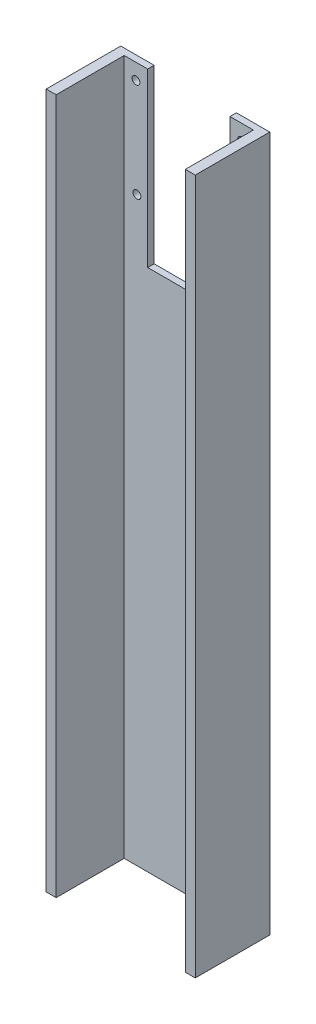
SolidWorks part; units mm, degrees
ref_plane "Front" through (0, 0, 0) normal (0, 0, 1) x (1, 0, 0)
ref_plane "Top" through (0, 0, 0) normal (0, 1, 0) x (1, 0, 0)
ref_plane "Right" through (0, 0, 0) normal (1, 0, 0) x (0, 0, -1)
sketch "Sketch1" plane through (0, 0, 0) normal (0, 1, 0) x (1, 0, 0)
  line L0 (-38.1, -19.05) -> (-33.02, -19.05)
  line L1 (-38.1, -19.05) -> (38.1, -19.05) construction
  line L2 (-38.1, -19.05) -> (-38.1, 19.05)
  line L3 (-38.1, 19.05) -> (38.1, 19.05)
  line L4 (38.1, -19.05) -> (38.1, 19.05)
  line L5 (-38.1, -19.05) -> (38.1, 19.05) construction
  line L6 (-38.1, 19.05) -> (38.1, -19.05) construction
  line L7 (-33.02, -19.05) -> (-33.02, 15.748)
  line L8 (-33.02, 15.748) -> (33.02, 15.748)
  line L9 (33.02, 15.748) -> (33.02, -19.05)
  line L10 (33.02, -19.05) -> (38.1, -19.05)
  point P0 (0, 0)
  dimension "D1" = 76.2
  dimension "D2" = 38.1
  dimension "D3" = 3.302
  dimension "D4" = 5.08
extrude "Boss-Extrude1" add sketch "Sketch1" along normal mid plane 355.6
sketch "Sketch2" plane through (0, 0, -15.748) normal (0, 0, 1) x (1, 0, 0)
  line L0 (-33.02, 177.8) -> (-33.02, -177.8) construction
  line L1 (-33.02, 177.8) -> (-27.0204, 177.8) construction
  line L2 (-33.02, 177.8) -> (-33.02, 169.8) construction
  line L3 (-33.02, 169.8) -> (-27.0204, 169.8) construction
  line L4 (-27.0204, 177.8) -> (-27.0204, 169.8) construction
  line L5 (-21.0207, 177.8) -> (-21.0207, 89.8924)
  line L6 (-33.02, 177.8) -> (33.02, 177.8) construction
  line L8 (-33.02, 177.8) -> (-21.0207, 177.8) construction
  line L9 (-21.0207, 89.8924) -> (0, 89.8924)
  line L10 (-21.0207, 177.8) -> (0, 177.8)
  line L11 (0, 177.8) -> (0, 89.8924)
  circle A0 centre (-27.0204, 169.8) radius 2
  circle A1 centre (-26.52, 119.4757) radius 2
  circle A2 centre (-13.52, 125.8257) radius 1.5 construction
  arc A3 (-13.52, 125.8257) -> (-14.5207, 111.3924) centre (-26.52, 119.4757) cw construction
  arc A4 (-13.2767, 110.5543) -> (-12.1722, 126.484) centre (-26.52, 119.4757) ccw construction
  arc A5 (-15.7648, 112.2304) -> (-14.8678, 125.1673) centre (-26.52, 119.4757) ccw construction
  arc A6 (-15.7648, 112.2304) -> (-13.2767, 110.5543) centre (-14.5207, 111.3924) ccw construction
  arc A7 (-12.1722, 126.484) -> (-14.8678, 125.1673) centre (-13.52, 125.8257) ccw construction
  point P10 (-12.0867, 118.475)
  dimension "D2" = 4
  dimension "D7" = 4
  dimension "D8" = 3
  dimension "D10" = 5
  dimension "D12" = 20
  dimension "D1" = 8
  dimension "D3" = 13
  dimension "D4" = 6.35
  dimension "D5" = 6.5
  dimension "D6" = 46
  dimension "D9" = 60
  dimension "D11" = 5.4993
extrude "Cut-Extrude1" cut sketch "Sketch2" against normal through all
mirror "Mirror1" about plane through (0, 0, 0) normal (1, 0, 0) of "Cut-Extrude1"
